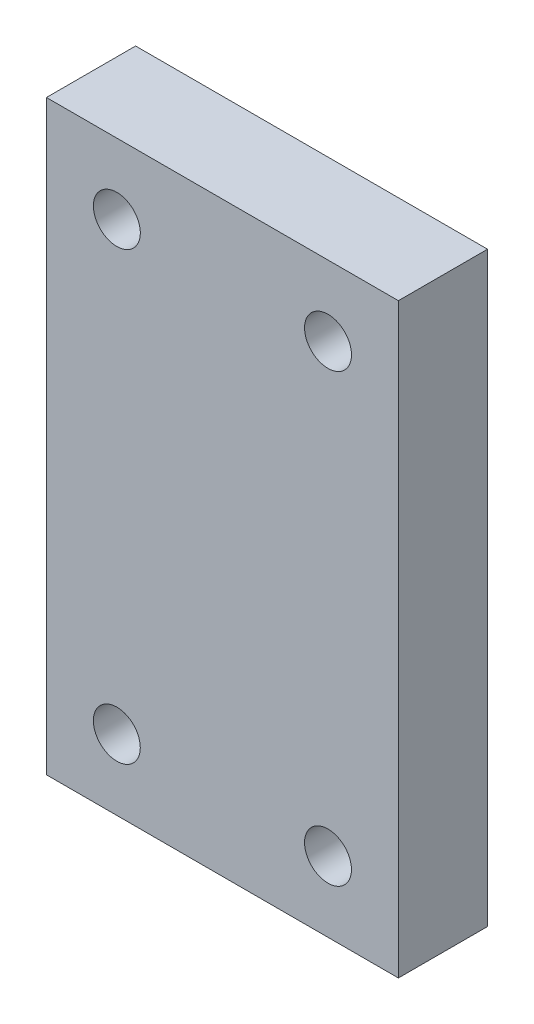
SolidWorks part; units mm, degrees
ref_plane "Front Plane" through (0, 0, 0) normal (0, 0, 1) x (1, 0, 0)
ref_plane "Top Plane" through (0, 0, 0) normal (0, 1, 0) x (1, 0, 0)
ref_plane "Right Plane" through (0, 0, 0) normal (1, 0, 0) x (0, 0, -1)
sketch "Sketch1" plane through (0, 0, 0) normal (0, 0, 1) x (1, 0, 0)
  line L0 (-29.5941, 119.0334) -> (-29.5941, 0.3078) construction
  line L1 (-48.6441, 94.1422) -> (-10.5441, 94.1422)
  line L2 (-48.6441, 94.1422) -> (-48.6441, 30.6422)
  line L3 (-48.6441, 30.6422) -> (-10.5441, 30.6422)
  line L4 (-10.5441, 94.1422) -> (-10.5441, 30.6422)
  line L5 (-48.6441, 94.1422) -> (-10.5441, 30.6422) construction
  line L6 (-48.6441, 30.6422) -> (-10.5441, 94.1422) construction
  line L7 (-82.748, 62.3922) -> (36.5001, 62.3922) construction
  line L8 (23.5598, 62.3922) -> (-95.6883, 62.3922) construction
  circle A0 centre (-41.0241, 38.2622) radius 2.54
  circle A1 centre (-18.1641, 38.2622) radius 2.54
  circle A2 centre (-18.1641, 86.5222) radius 2.54
  circle A3 centre (-41.0241, 86.5222) radius 2.54
  point P0 (-29.5941, 62.3922)
  dimension "D1" = 7.62
  dimension "D2" = 7.62
  dimension "D3" = 38.1
  dimension "D4" = 63.5
extrude "Boss-Extrude1" add sketch "Sketch1" along normal blind 9.652
